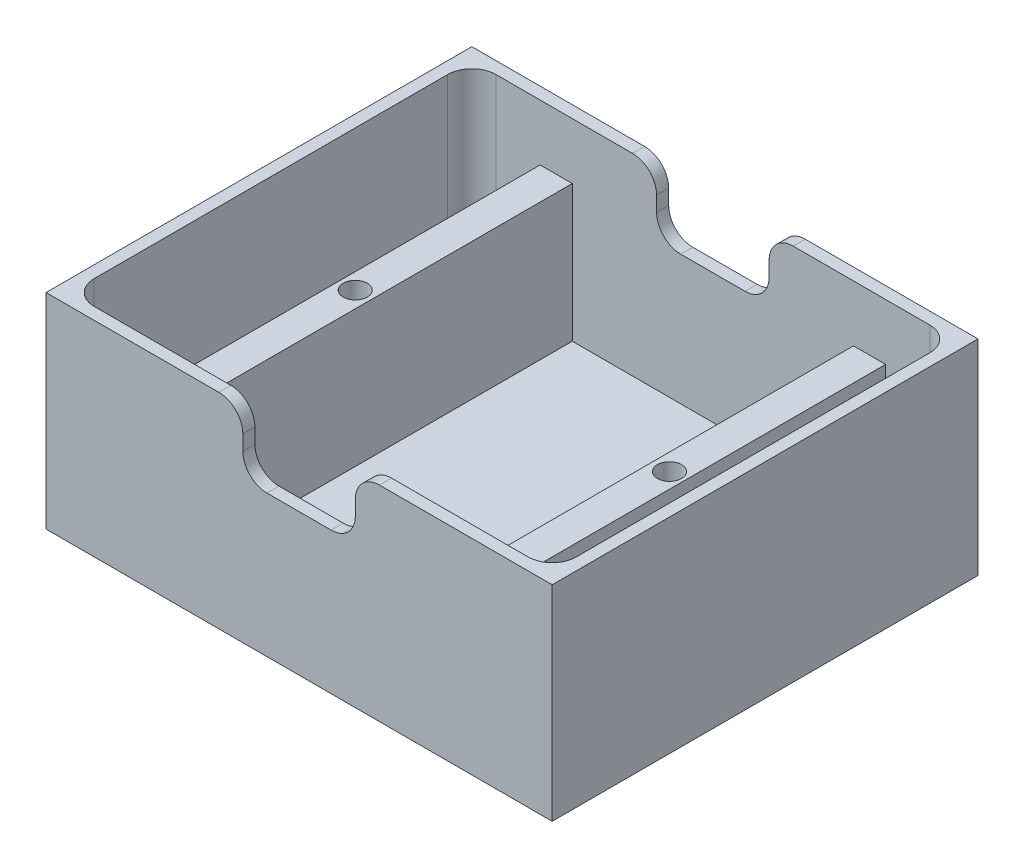
SolidWorks part; units mm, degrees
ref_plane "Front Plane" through (0, 0, 0) normal (0, 0, 1) x (1, 0, 0)
ref_plane "Top Plane" through (0, 0, 0) normal (0, 1, 0) x (1, 0, 0)
ref_plane "Right Plane" through (0, 0, 0) normal (1, 0, 0) x (0, 0, -1)
sketch "Sketch1" plane through (0, 0, 0) normal (0, 1, 0) x (1, 0, 0)
  line L1 (0, 0) -> (60, 0)
  line L2 (0, 0) -> (0, -50)
  line L3 (0, -50) -> (60, -50)
  line L4 (60, 0) -> (60, -50)
  dimension "D1" = 60
  dimension "D2" = 50
extrude "Boss-Extrude1" add sketch "Sketch1" along normal blind 24
shell "Shell1" thickness 1.5 removed face at (30, 24, 25) outward yes
sketch "Sketch2" plane through (0, 0, 0) normal (0, 1, 0) x (1, 0, 0)
  line L0 (60, 0) -> (0, 0) construction
  line L1 (8.5, 0) -> (12.5, 0)
  line L2 (8.5, 0) -> (8.5, -50)
  line L3 (8.5, -50) -> (12.5, -50)
  line L4 (12.5, 0) -> (12.5, -50)
  line L5 (0, -50) -> (60, -50) construction
  line L6 (30, 0) -> (30, -71.172) construction
  line L7 (51.5, -50) -> (47.5, -50)
  line L8 (47.5, 0) -> (47.5, -50)
  line L9 (51.5, 0) -> (47.5, 0)
  line L10 (51.5, 0) -> (51.5, -50)
  dimension "D1" = 4
  dimension "D2" = 17.5
extrude "Boss-Extrude2" add sketch "Sketch2" along normal blind 17
sketch "Sketch3" plane through (0, 0, 0) normal (0, 1, 0) x (1, 0, 0)
  line L0 (-7.5821, -25) -> (66.7821, -25) construction
  point P2 (-7.5821, -25)
  point P3 (0, 0)
  point P4 (0, 0)
  point P5 (12.5, -25)
  point P6 (7.7093, -19.7979)
sketch "Sketch4" plane through (0, 17, 0) normal (0, 1, 0) x (1, 0, 0)
  line L0 (29.6, -25) -> (29.6, -55.4073) construction
  line L1 (-7.5821, -25) -> (66.7821, -25) construction
  circle A0 centre (10.49, -25) radius 1.5
  circle A1 centre (49.6004, -25) radius 1.5
  point P8 (49.4426, -25)
  point P9 (10.4244, -25)
  point P10 (49.6004, -25)
  point P11 (10.7814, -25)
  point P12 (10.49, -25)
extrude "Cut-Extrude1" cut sketch "Sketch4" against normal blind 8
sketch "Sketch6" plane through (0, 0, 51.5) normal (0, 0, 1) x (1, 0, 0)
  line L0 (30, 24) -> (30, -9.6606) construction
  line L1 (23, 16.1347) -> (37, 16.1347)
  line L2 (23, 16.1347) -> (23, 28.1347)
  line L3 (23, 28.1347) -> (37, 28.1347)
  line L4 (37, 16.1347) -> (37, 28.1347)
  line L5 (-1.5, 24) -> (61.5, 24) construction
  dimension "D1" = 14
  dimension "D2" = 7
  dimension "D3" = 12
extrude "Cut-Extrude2" cut sketch "Sketch6" against normal blind 58
fillet "Fillet1" radius 3 12 edges at (60, 12, 50) (0, 12, 50) (60, 12, 0) (0, 12, 0) (23, 24, -0.75) (23, 16.1347, -0.75) (37, 16.1347, -0.75) (37, 24, -0.75) (23, 24, 50.75) (23, 16.1347, 50.75) (37, 16.1347, 50.75) (37, 24, 50.75)
